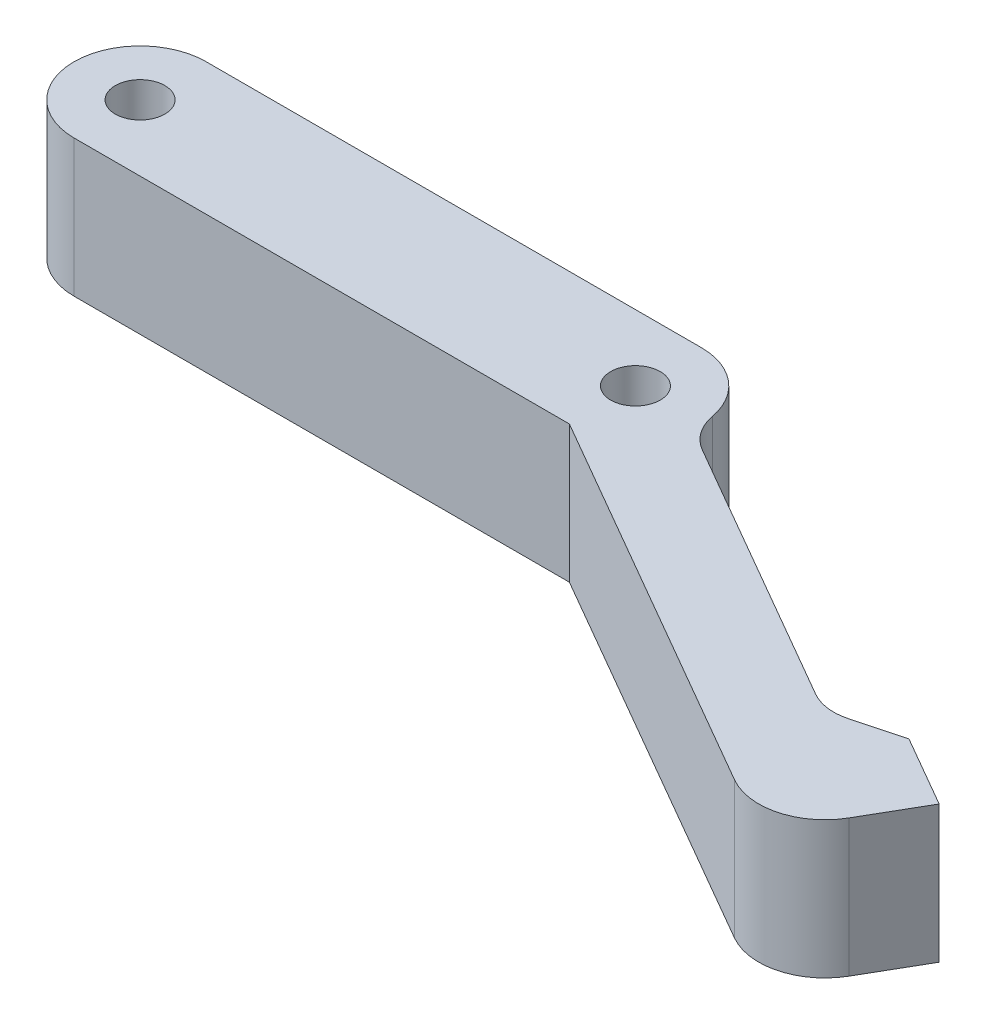
SolidWorks part; units mm, degrees
ref_plane "Front Plane" through (0, 0, 0) normal (0, 0, 1) x (1, 0, 0)
ref_plane "Top Plane" through (0, 0, 0) normal (0, 1, 0) x (1, 0, 0)
ref_plane "Right Plane" through (0, 0, 0) normal (1, 0, 0) x (0, 0, -1)
sketch "Sketch1" plane through (0, 0, 0) normal (0, 1, 0) x (1, 0, 0)
  line L0 (0, 0) -> (30, 0) construction
  line L1 (0, 4) -> (30, 4)
  line L2 (33.9665, -0.5166) -> (52.6992, -11.3319)
  line L3 (30, -4) -> (30, 4) construction
  line L4 (52.6992, -11.3319) -> (56.7972, -10.2338)
  line L5 (0, -4) -> (30, -4)
  line L6 (56.7972, -10.2338) -> (61.1274, -12.7338)
  line L7 (59.1274, -16.1979) -> (61.1274, -12.7338)
  line L8 (53.6633, -17.662) -> (30, -4)
  circle A0 centre (0, 0) radius 1.5
  circle A1 centre (30, 0) radius 1.5
  arc A2 (0, 4) -> (0, -4) centre (0, 0) ccw
  arc A6 (53.6633, -17.662) -> (59.1274, -16.1979) centre (55.6633, -14.1979) ccw
  arc A7 (33.9665, -0.5166) -> (30, 4) centre (30, 0) ccw
  dimension "D2" = 3
  dimension "D3" = 8
  dimension "D1" = 30
  dimension "D4" = 210
  dimension "D6" = 135
  dimension "D7" = 5
  dimension "D8" = 5
  dimension "D9" = 4
extrude "Boss-Extrude1" add sketch "Sketch1" along normal blind 8.3 contours L1 A2 A1 L5 | A0 A2 region at (26.8351, 0, 3.8069)
fillet "Fillet1" radius 3 2 edges at (52.6992, 4.15, 11.3319) (33.9665, 4.15, 0.5166)
